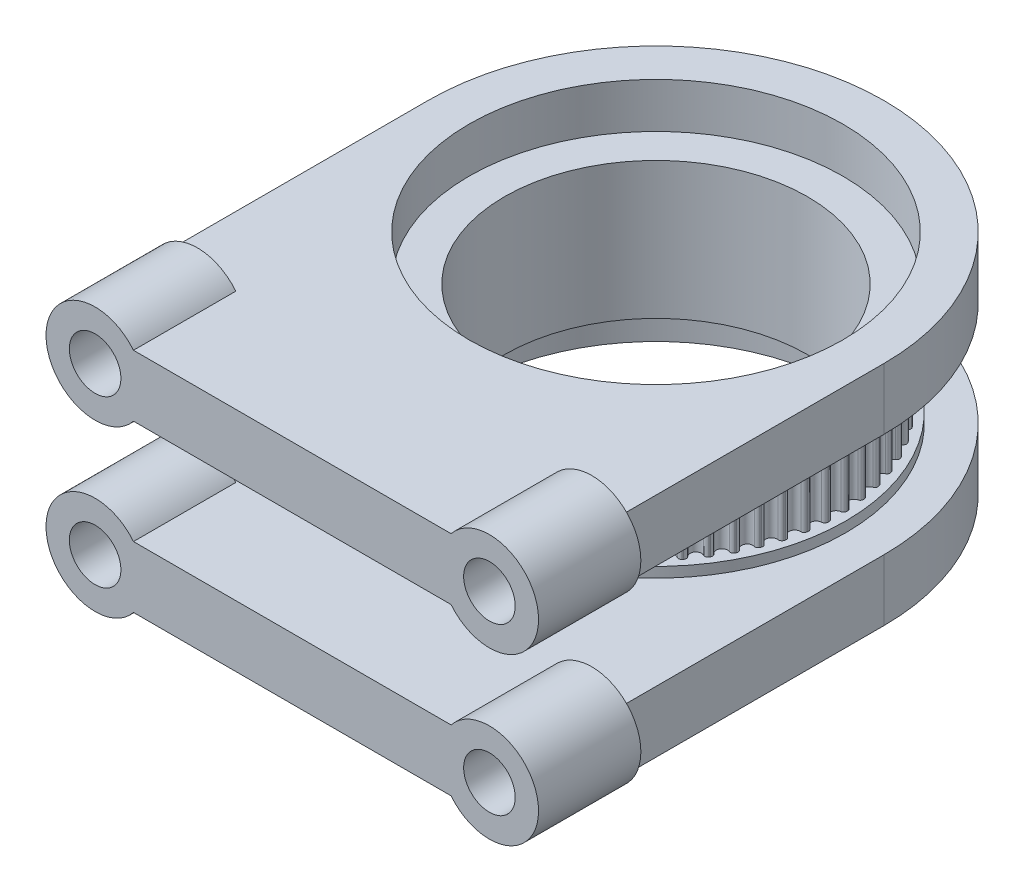
SolidWorks part; units mm, degrees
ref_plane "Front Plane" through (0, 0, 0) normal (0, 0, 1) x (1, 0, 0)
ref_plane "Top Plane" through (0, 0, 0) normal (0, 1, 0) x (1, 0, 0)
ref_plane "Right Plane" through (0, 0, 0) normal (1, 0, 0) x (0, 0, -1)
sketch "Sketch1" plane through (0, 0, 0) normal (0, 1, 0) x (1, 0, 0)
  line L0 (0, 0) -> (0, 28.2667) construction
  line L1 (0, 0) -> (2.9202, 27.7837) construction
  circle A0 centre (0, 0) radius 28.2667 construction
  circle A1 centre (0, 0) radius 27.0467 construction
  circle A2 centre (0, 27.9367) radius 0.89 construction
  circle A5 centre (2.9202, 27.7837) radius 0.89 construction
  arc A6 (0, 27.0467) -> (0.8804, 27.8061) centre (0, 27.9367) ccw
  arc A7 (0.8804, 27.8061) -> (1.3997, 28.2321) centre (1.3749, 27.7327) cw
  arc A8 (1.559, 28.2237) -> (2.031, 27.7458) centre (1.5314, 27.7245) cw
  arc A9 (2.8272, 26.8986) -> (2.031, 27.7458) centre (2.9202, 27.7837) cw
  arc A10 (1.3997, 28.2321) -> (1.559, 28.2237) centre (0, 0) cw
  arc A11 (0, 27.0467) -> (2.8272, 26.8986) centre (0, 0) ccw
  dimension "D1" = 56.5335
  dimension "D3" = 1.78
  dimension "D4" = 0.5
  dimension "D2" = 1.22
  dimension "D5" = 6
extrude "Boss-Extrude1" add sketch "Sketch1" along normal mid plane 13 contours A6 A11 A9 A8 A7 region at (0.001, 0, -0.0192)
ref_axis "Axis1" through (0, 3.3, 0) along (0, -1, 0)
pattern_circular "CirPattern1" count 60 over 360 about axis through (0, 3.3, 0) along (0, -1, 0) of "Boss-Extrude1"
sketch "Sketch2" plane through (0, 0, 0) normal (1, 0, 0) x (0, 0, -1)
  line L10 (0, 6.5) -> (29.4415, 6.5) construction
  line L11 (0, 6.5) -> (0, 8.0875) construction
  line L12 (0, 8.0875) -> (29.4415, 8.0875) construction
  line L15 (29.4415, 6.5) -> (29.4415, 8.0875) construction
  line L20 (0, 3.3) -> (0, -3.3) construction
  line L22 (29.4415, 8.0875) -> (0, 8.0875)
  line L23 (29.4415, 8.0875) -> (29.4415, 6.5)
  line L24 (29.4415, 6.5) -> (0, 6.5)
  line L25 (0, 8.0875) -> (0, 6.5)
  dimension "D1" = 1.5875
  dimension "D2" = 29.4415
  dimension "D3" = 6.5
revolve "Revolve3" add sketch "Sketch2" angle 360 about axis through (0, 3.3, 0) along (0, -1, 0) region at (0, 7.2937, -14.7207)
mirror "Mirror1" about plane through (0, 0, 0) normal (0, 1, 0) of "Revolve3"
sketch "Sketch4" plane through (0, 8.0875, 0) normal (0, 1, 0) x (1, 0, 0)
  line L0 (-35.35, 0) -> (-35.35, -56.429)
  line L1 (-35.35, -56.429) -> (35.35, -56.429)
  line L2 (35.35, -56.429) -> (35.35, 0)
  line L3 (0, -29.4415) -> (0, -56.429) construction
  arc A0 (-35.35, 0) -> (35.35, 0) centre (0, 0) cw
  circle A1 centre (0, 0) radius 29.4415 construction
  circle A3 centre (0, 0) radius 29 construction
  dimension "D2" = 58
  dimension "D3" = 6.35
  dimension "D1" = 26.9875
extrude "Boss-Extrude3" add sketch "Sketch4" along normal blind 9.525
sketch "Sketch9" plane through (0, 17.6125, 0) normal (0, 1, 0) x (1, 0, 0)
  circle A0 centre (0, 0) radius 29
  dimension "D1" = 58
extrude "Cut-Extrude2" cut sketch "Sketch9" against normal blind 7
mirror "Mirror5" about plane through (0, 0, 0) normal (0, 1, 0) of "Cut-Extrude2", "Boss-Extrude3"
sketch "Sketch10" plane through (0, 0, 0) normal (0, 1, 0) x (1, 0, 0)
  circle A0 centre (0, 0) radius 23.5
  dimension "D1" = 47
extrude "Cut-Extrude3" cut sketch "Sketch10" against normal through all both and the other way through all
ref_axis "Axis2" through (0, 0, -38.9864) along (0, 0, 1)
sketch "Sketch11" plane through (0, 0, 56.429) normal (0, 0, 1) x (1, 0, 0)
  line L0 (30.5875, -17.6125) -> (30.5875, -12.85) construction
  line L1 (-35.35, -17.6125) -> (35.35, -17.6125) construction
  line L2 (30.5875, -12.85) -> (35.35, -12.85) construction
  line L3 (35.35, -17.6125) -> (35.35, -8.0875) construction
  circle A0 centre (30.5875, -12.85) radius 7.62
  circle A1 centre (30.5875, -12.85) radius 4
  line M1 (35.35, -8.0875) -> (-35.35, -8.0875)
  line M3 (-35.35, -17.6125) -> (35.35, -17.6125)
  line M4 (35.35, -17.6125) -> (35.35, -8.0875)
  dimension "D1" = 15.24
  dimension "D2" = 8
extrude "Cut-Extrude4" cut sketch "Sketch11" against normal blind 12.7 contours A1 region at (30.5875, -12.85, 56.429)
extrude "Boss-Extrude4" add sketch "Sketch11<3>" against normal blind 15.875 contours A0 M3 M1 M4 | A0 A1 M1 M3 M4 region at (33.0436, -19.8474, 56.429) region at (29.9946, -8.2437, 56.429)
sketch "Sketch11<3>" plane through (0, 0, 56.429) normal (0, 0, 1) x (1, 0, 0) same geometry as "Sketch11"
mirror "Mirror6" about plane through (0, 0, 0) normal (0, 1, 0) of "Boss-Extrude4", "Cut-Extrude4"
mirror "Mirror7" about plane through (0, 0, 0) normal (1, 0, 0) of "Mirror6", "Boss-Extrude4", "Cut-Extrude4"
equation "\"TEETH_NUM\"= 60"
equation "\"TOOTH_PITCH\"= 3mm"
equation "\"PITCH_LINE_OFFSET\"= .015in"
equation "\"DIAMETER_PER_GROOVE\"= \"OUTSIDE_DIAMETER\" / \"TEETH_NUM\" * 1in"
equation "\"PITCH_DIAMETER\"= ( ( \"TEETH_NUM\" * 3 - 1.31 ) / 3.1415 + .415 ) * 1mm"
equation "\"OUTSIDE_DIAMETER\"= \"PITCH_DIAMETER\" - \"PITCH_LINE_OFFSET\" * 2"
equation "\"D1@Sketch1\"=\"OUTSIDE_DIAMETER\""
equation "\"TOOTH_HEIGHT\"= 1.22mm"
equation "\"D2@Sketch1\"=\"TOOTH_HEIGHT\""
equation "\"TOOTH_DIAMETER\"= 1.78mm"
equation "\"INTERNAL_RADIUS\"= .5mm"
equation "\"D3@Sketch1\"=\"TOOTH_DIAMETER\""
equation "\"D5@Sketch1\"=360 / \"TEETH_NUM\""
equation "\"D4@Sketch1\"=\"INTERNAL_RADIUS\""
equation "\"D1@CirPattern1\"=\"TEETH_NUM\""
equation "\"BELT_GAP\"= 13mm"
equation "\"D2@Sketch2\"=\"PITCH_DIAMETER\"/2+1/32"
equation "\"D3@Sketch2\"=\"BELT_GAP\"/2"
equation "\"D1@Boss-Extrude1\"=\"BELT_GAP\""
